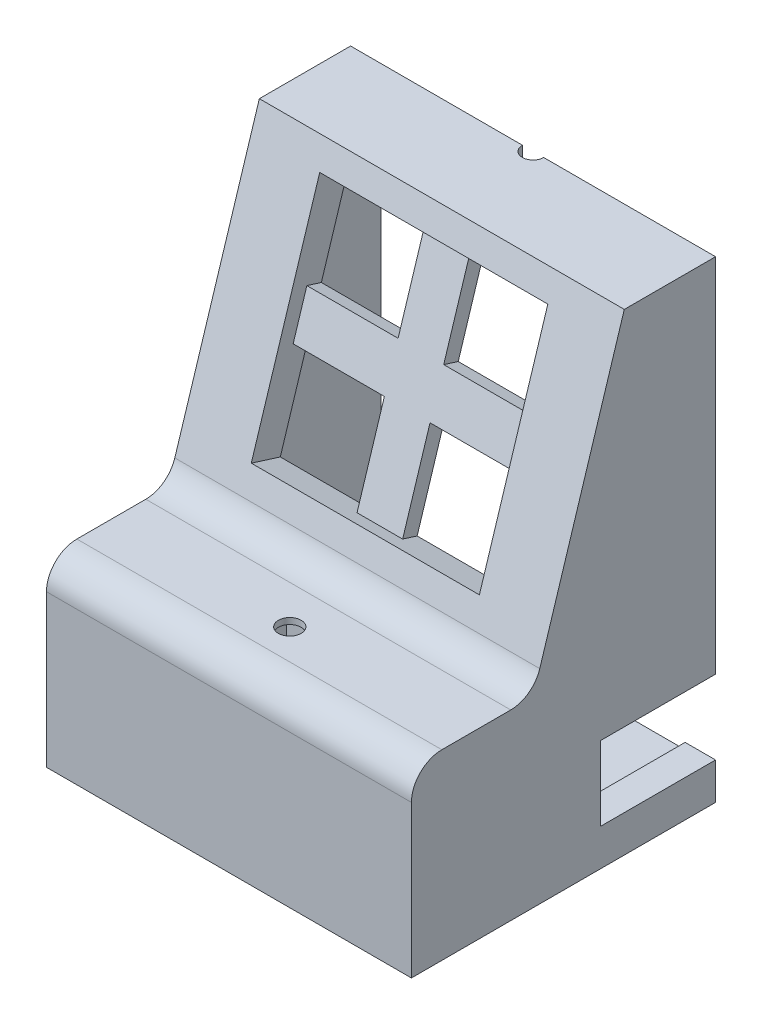
SolidWorks part; units mm, degrees
ref_plane "Plan de face" through (0, 0, 0) normal (0, 0, 1) x (1, 0, 0)
ref_plane "Plan de dessus" through (0, 0, 0) normal (0, 1, 0) x (1, 0, 0)
ref_plane "Plan de droite" through (0, 0, 0) normal (1, 0, 0) x (0, 0, -1)
sketch "Esquisse1" plane through (0, 0, 0) normal (1, 0, 0) x (0, 0, -1)
  line L0 (0, 0) -> (-100, 0)
  line L1 (-100, 0) -> (-100, 50)
  line L2 (-90, 60) -> (-67.338, 60)
  line L3 (-57.7986, 67) -> (-30, 155.3939)
  line L4 (-30, 155.3939) -> (0, 155.3939)
  line L5 (0, 155.3939) -> (0, 0)
  arc A0 (-67.338, 60) -> (-57.7986, 67) centre (-67.338, 70) ccw
  arc A1 (-100, 50) -> (-90, 60) centre (-90, 50) cw
  point P9 (-60, 60)
  point P12 (-100, 60)
  dimension "D6" = 10
  dimension "D1" = 100
  dimension "D2" = 60
  dimension "D3" = 100
  dimension "D4" = 40
  dimension "D5" = 30
extrude "Boss.-Extru.1" add sketch "Esquisse1" along normal blind 120
shell "Coque1" thickness 10 removed face at (60, 77.697, 0)
ref_plane "Plan1" through (0, 22.5709, 71.7709) normal (0, -0.3, -0.9539) x (-1, 0, 0)
sketch "Esquisse3" plane through (0, 22.5709, 71.7709) normal (0, -0.3, -0.9539) x (-1, 0, 0)
  line L1 (-22.5, 130.4053) -> (-97.5, 130.4053)
  line L2 (-22.5, 130.4053) -> (-22.5, 55.4053)
  line L3 (-22.5, 55.4053) -> (-97.5, 55.4053)
  line L4 (-97.5, 130.4053) -> (-97.5, 55.4053)
  line L5 (-120, 139.2364) -> (0, 139.2364) construction
  line L6 (0, 139.2364) -> (0, 46.5743) construction
  point P4 (-60, 130.4053)
  point P7 (-60, 139.2364)
  point P10 (0, 92.9053)
  point P11 (-22.5, 92.9053)
  dimension "D1" = 75
  dimension "D2" = 75
  dimension "D3" = 0
extrude "Enlèv. mat.-Extru.1" cut sketch "Esquisse3" along normal blind 5
sketch "Esquisse4" plane through (0, 22.5709, 71.7709) normal (0, -0.3, -0.9539) x (-1, 0, 0)
  line L0 (-60, 130.4053) -> (-60, 55.4053) construction
  line L1 (-22.5, 130.4053) -> (-52.5, 130.4053)
  line L2 (-22.5, 130.4053) -> (-22.5, 100.4053)
  line L3 (-22.5, 100.4053) -> (-52.5, 100.4053)
  line L4 (-52.5, 130.4053) -> (-52.5, 100.4053)
  line L5 (-22.5, 130.4053) -> (-97.5, 130.4053) construction
  line L6 (-97.5, 55.4053) -> (-22.5, 55.4053) construction
  line L7 (-22.5, 92.9053) -> (-97.5, 92.9053) construction
  line L8 (-22.5, 55.4053) -> (-22.5, 130.4053) construction
  line L9 (-97.5, 130.4053) -> (-97.5, 55.4053) construction
  line L10 (-22.5, 55.4053) -> (-22.5, 85.4053)
  line L11 (-22.5, 55.4053) -> (-52.5, 55.4053)
  line L12 (-52.5, 55.4053) -> (-52.5, 85.4053)
  line L13 (-22.5, 85.4053) -> (-52.5, 85.4053)
  line L14 (-97.5, 130.4053) -> (-67.5, 130.4053)
  line L15 (-97.5, 130.4053) -> (-97.5, 100.4053)
  line L16 (-97.5, 55.4053) -> (-97.5, 85.4053)
  line L17 (-97.5, 55.4053) -> (-67.5, 55.4053)
  line L18 (-67.5, 55.4053) -> (-67.5, 85.4053)
  line L19 (-67.5, 130.4053) -> (-67.5, 100.4053)
  line L20 (-97.5, 100.4053) -> (-67.5, 100.4053)
  line L21 (-97.5, 85.4053) -> (-67.5, 85.4053)
  dimension "D1" = 30
  dimension "D2" = 30
extrude "Enlèv. mat.-Extru.2" cut sketch "Esquisse4" along normal up to next
sketch "Esquisse5" plane through (0, 0, 0) normal (0, 0, -1) x (-1, 0, 0)
  line L0 (-60, 155.3939) -> (-60, 0) construction
  line L1 (-120, 155.3939) -> (0, 155.3939) construction
  line L2 (-120, 0) -> (0, 0) construction
  line L3 (-120, 77.697) -> (0, 77.697) construction
  line L4 (-120, 0) -> (-120, 155.3939) construction
  line L5 (0, 0) -> (0, 155.3939) construction
  circle A0 centre (-114.7157, 149.9262) radius 3.25
  circle A1 centre (-5.2843, 149.9262) radius 3.25
  circle A2 centre (-5.2843, 5.4677) radius 3.25
  circle A3 centre (-114.7157, 5.4677) radius 3.25
  dimension "D1" = 6.5
extrude "Enlèv. mat.-Extru.3" cut sketch "Esquisse5" against normal blind 3.5
sketch "Esquisse6" plane through (0, 0, 0) normal (0, 1, 0) x (1, 0, 0)
  line L2 (120, -67.338) -> (0, -67.338) construction
  line L3 (120, -100) -> (0, -100) construction
  circle A0 centre (60, -80) radius 3.75
  point P9 (60, -67.338)
  dimension "D1" = 7.5
  dimension "D2" = 20
extrude "Enlèv. mat.-Extru.4" cut sketch "Esquisse6" along normal up to next from surface starting at face at (60, 50, 78.669)
sketch "Esquisse7" plane through (0, 0, 0) normal (0, 1, 0) x (1, 0, 0)
  line L0 (60, -67.338) -> (60, -90) construction
  line L1 (53, -74) -> (67, -74)
  line L2 (53, -74) -> (53, -86)
  line L3 (53, -86) -> (67, -86)
  line L4 (67, -74) -> (67, -86)
  line L5 (120, -67.338) -> (0, -67.338) construction
  line L6 (120, -90) -> (0, -90) construction
  line L7 (60, -80) -> (120, -80) construction
  line L8 (120, -67.338) -> (120, -90) construction
  line L9 (60, -80) -> (0, -80) construction
  line L10 (0, -67.338) -> (0, -90) construction
  point P16 (60, -74)
  point P17 (67, -80)
  dimension "D1" = 14
  dimension "D2" = 12
extrude "Enlèv. mat.-Extru.5" cut sketch "Esquisse7" along normal blind 8 from surface starting at face at (60, 50, 76.25)
sketch "Esquisse8" plane through (120, 0, 0) normal (1, 0, 0) x (0, 0, -1)
  line L0 (0, 0) -> (0, 155.3939) construction
  line L1 (-37.8409, 36.5116) -> (0, 36.5116)
  line L2 (-37.8409, 36.5116) -> (-37.8409, 12.0971)
  line L3 (-37.8409, 12.0971) -> (0, 12.0971)
  line L4 (0, 36.5116) -> (0, 12.0971)
  point P4 (0, 36.5116)
  point P7 (0, 0)
  dimension "D1" = 37.8409
  dimension "D2" = 24.4145
extrude "Enlèv. mat.-Extru.6" cut sketch "Esquisse8" against normal blind 10
sketch "Esquisse9" plane through (0, 0, 0) normal (0, 1, 0) x (1, 0, 0)
  line L0 (120, 0) -> (0, 0) construction
  circle A0 centre (60, 0) radius 3.5
  dimension "D1" = 7
extrude "Enlèv. mat.-Extru.8" cut sketch "Esquisse9" along normal blind 25 from surface starting at face at (60, 145.3939, 11.331)
